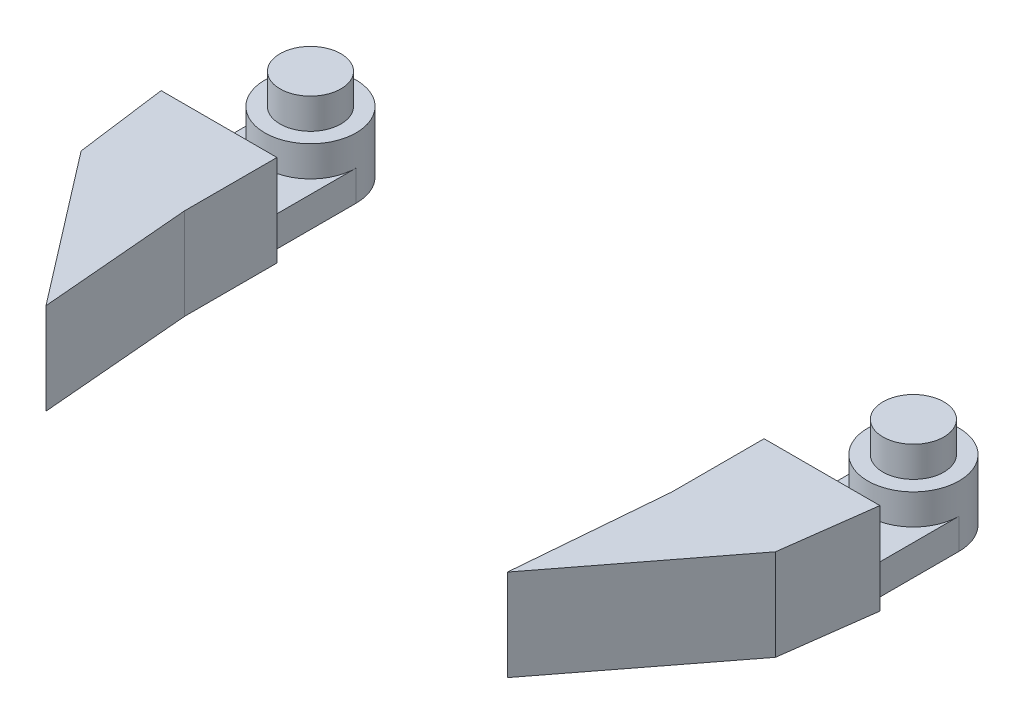
SolidWorks part; units mm, degrees
ref_plane "Front Plane" through (0, 0, 0) normal (0, 0, 1) x (1, 0, 0)
ref_plane "Top Plane" through (0, 0, 0) normal (0, 1, 0) x (1, 0, 0)
ref_plane "Right Plane" through (0, 0, 0) normal (1, 0, 0) x (0, 0, -1)
sketch "Sketch1" plane through (0, 0, 0) normal (0, 1, 0) x (1, 0, 0)
  line L6 (-9.5, -15) -> (-7.5, -30.1272)
  line L7 (-7.5, -30.1272) -> (11.6074, -55)
  line L8 (11.6074, -55) -> (9.5, -30.1272)
  line L9 (9.5, -30.1272) -> (9.5, -15)
  line L10 (9.5, -15) -> (-9.5, -15)
  line L11 (49.4645, 12.4217) -> (49.4645, -55.9334) construction
  line L12 (-7.5, 0) -> (7.5, 0)
  line L13 (-7.5, 0) -> (-7.5, -15)
  line L14 (-7.5, -15) -> (7.5, -15)
  line L15 (7.5, 0) -> (7.5, -15)
  line L16 (91.429, 0) -> (91.429, -15)
  line L17 (106.429, -15) -> (91.429, -15)
  line L18 (106.429, 0) -> (106.429, -15)
  line L19 (106.429, 0) -> (91.429, 0)
  line L20 (89.429, -15) -> (108.429, -15)
  line L21 (89.429, -30.1272) -> (89.429, -15)
  line L22 (87.3217, -55) -> (89.429, -30.1272)
  line L23 (106.429, -30.1272) -> (87.3217, -55)
  line L24 (108.429, -15) -> (106.429, -30.1272)
  circle A0 centre (0, 0) radius 5
  circle A1 centre (0, 0) radius 7.5
  circle A2 centre (98.929, 0) radius 7.5
  circle A3 centre (98.929, 0) radius 5
  point P12 (0, 0)
  point P16 (0, -15)
  point P17 (0, -15)
  dimension "D1" = 10
  dimension "D7" = 15
  dimension "D2" = 19
  dimension "D3" = 40
  dimension "D4" = 150
  dimension "D6" = 15
extrude "Boss-Extrude1" add sketch "Sketch1" along normal blind 10 contours L12 A1 A0 | L12 A1 A0 region at (0, 0, -7.3323) region at (-6.25, 0, 0.1677)
extrude "Boss-Extrude2" add sketch "Sketch1<3>" along normal blind 15 separate body contours L9 L10 L6 L7 L8 region at (2.2588, 0, 29.4144)
sketch "Sketch1<3>" plane through (0, 0, 0) normal (0, 1, 0) x (1, 0, 0) same geometry as "Sketch1"
extrude "Boss-Extrude3" add sketch "Sketch1<4>" along normal blind 5 contours A1 L13 L10 L15 region at (0, 0, 10.2914)
sketch "Sketch1<4>" plane through (0, 0, 0) normal (0, 1, 0) x (1, 0, 0) same geometry as "Sketch1"
extrude "Boss-Extrude4" add sketch "Sketch1<5>" along normal blind 15 contours L12 A0 | L12 A0 region at (0, 0, -2.1221) region at (0, 0, 2.1221)
sketch "Sketch1<5>" plane through (0, 0, 0) normal (0, 1, 0) x (1, 0, 0) same geometry as "Sketch1"
extrude "Boss-Extrude5" add sketch "Sketch1<6>" along normal blind 15 separate body contours A3 L19 | A3 L19 region at (98.929, 0, -2.1221) region at (98.929, 0, 2.1221)
sketch "Sketch1<6>" plane through (0, 0, 0) normal (0, 1, 0) x (1, 0, 0) same geometry as "Sketch1"
extrude "Boss-Extrude6" add sketch "Sketch1<7>" along normal blind 10 contours L19 A3 A2 | L19 A3 A2 region at (98.929, 0, -7.3323) region at (92.679, 0, 0.1677)
sketch "Sketch1<7>" plane through (0, 0, 0) normal (0, 1, 0) x (1, 0, 0) same geometry as "Sketch1"
extrude "Boss-Extrude7" add sketch "Sketch1<8>" along normal blind 5 contours L18 A2 L16 L17 region at (98.929, 0, 10.2914)
sketch "Sketch1<8>" plane through (0, 0, 0) normal (0, 1, 0) x (1, 0, 0) same geometry as "Sketch1"
extrude "Boss-Extrude8" add sketch "Sketch1<9>" along normal blind 15 contours L24 L20 L17 L21 L22 L23 region at (96.6703, 0, 29.4144)
sketch "Sketch1<9>" plane through (0, 0, 0) normal (0, 1, 0) x (1, 0, 0) same geometry as "Sketch1"
